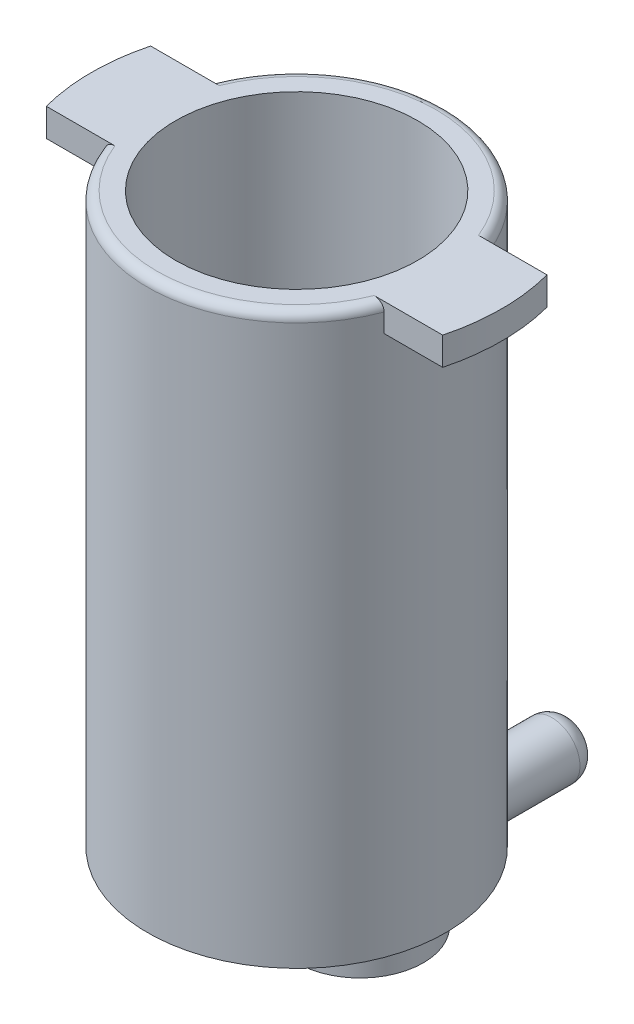
SolidWorks part; units mm, degrees
ref_plane "Front Plane" through (0, 0, 0) normal (0, 0, 1) x (1, 0, 0)
ref_plane "Top Plane" through (0, 0, 0) normal (0, 1, 0) x (1, 0, 0)
ref_plane "Right Plane" through (0, 0, 0) normal (1, 0, 0) x (0, 0, -1)
sketch "Sketch1" plane through (0, 0, 0) normal (0, 1, 0) x (1, 0, 0)
  circle A0 centre (0, 0) radius 8
extrude "Boss-Extrude1" add sketch "Sketch1" along normal blind 30.5
shell "Shell1" thickness 1.5 removed face at (0, 30.5, 8)
sketch "Sketch2" plane through (0, 0, 0) normal (0, -1, 0) x (1, 0, 0)
  circle A0 centre (0, -3.4) radius 3.4
extrude "Boss-Extrude2" add sketch "Sketch2" along normal blind 5.4 contours A0
shell "Shell2" thickness 1.5 removed face at (0, 1.5, 6.5)
sketch "Sketch4" plane through (0, 0, 0) normal (0, -1, 0) x (1, 0, 0)
  line L0 (-3.4, -3.4) -> (3.4, -3.4) construction
  circle A0 centre (0, -3.4) radius 3.4 construction
  circle A1 centre (0, -3.4) radius 3.4 construction
ref_plane "Plane1" through (0, 0, -3.4) normal (0, 0, 1) x (1, 0, 0)
sketch "Sketch5" plane through (0, 0, -3.4) normal (0, 0, 1) x (1, 0, 0)
  line L0 (0, 0) -> (0, -5.4) construction
  line L1 (-3.4, -5.4) -> (3.4, -5.4) construction
  circle A0 centre (0, -2.3538) radius 2.45
  point P2 (0, 0)
  point P5 (0, 0)
  point P8 (0, 0)
  point P9 (0, 0)
  point P10 (0, -2.3538)
extrude "Boss-Extrude5" add sketch "Sketch5" against normal blind 4.9
sketch "Sketch6" plane through (0, 0, -8.3) normal (0, 0, -1) x (-1, 0, 0)
  circle A0 centre (0, -2.3538) radius 1.5
extrude "Boss-Extrude6" add sketch "Sketch6" along normal blind 6.3
sketch "Sketch7" plane through (0, 0, -14.6) normal (0, 0, -1) x (-1, 0, 0)
  circle A0 centre (0, -2.3538) radius 0.95
extrude "Cut-Extrude1" cut sketch "Sketch7" against normal blind 11.3
sketch "Sketch8" plane through (0, -3.9, 0) normal (0, 1, 0) x (1, 0, 0)
  line L0 (-3.4, 3.4) -> (3.4, 3.4) construction
  circle A0 centre (0, 3.4) radius 1.9
extrude "Cut-Extrude2" cut sketch "Sketch8" along normal through all contours A0
fillet "Fillet1" radius 1 1 edges at (-1.5, -2.3538, -14.6)
fillet "Fillet2" radius 0.5 1 edges at (0, 30.5, 8)
sketch "Sketch9" plane through (0, 30.5, 0) normal (0, 1, 0) x (1, 0, 0)
  line L0 (0, 1.3156) -> (0, -1.546) construction
  line L3 (-10.6377, 2.8) -> (-5.866, 2.8)
  line L4 (-10.6377, -2.8) -> (-5.866, -2.8)
  arc A1 (-5.866, 2.8) -> (-5.866, -2.8) centre (0, 0) ccw
  arc A2 (-10.6377, 2.8) -> (-10.6377, -2.8) centre (0, 0) ccw
  circle A3 centre (0, 0) radius 6.5 construction
  circle A4 centre (0, 0) radius 6.5 construction
extrude "Boss-Extrude7" add sketch "Sketch9" against normal blind 1.5
mirror "Mirror1" about plane through (0, 0, 0) normal (1, 0, 0) of bodies 107
